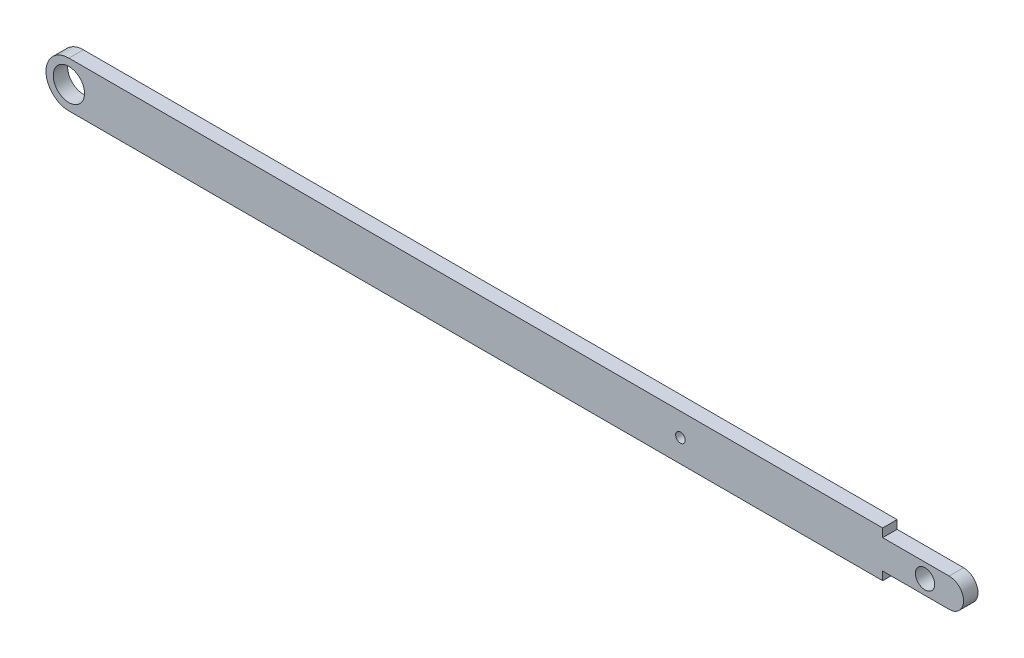
SolidWorks part; units mm, degrees
material "Gray Cast Iron"
ref_plane "Front Plane" through (0, 0, 0) normal (0, 0, 1) x (1, 0, 0)
ref_plane "Top Plane" through (0, 0, 0) normal (0, 1, 0) x (1, 0, 0)
ref_plane "Right Plane" through (0, 0, 0) normal (1, 0, 0) x (0, 0, -1)
sketch "Sketch1" plane through (0, 0, 0) normal (0, 0, 1) x (1, 0, 0)
  line L0 (0, -4.75) -> (169, -4.75)
  line L1 (169, -4.75) -> (169, -3)
  line L2 (169, -3) -> (182.8, -3)
  line L3 (182.8, 3) -> (169, 3)
  line L4 (169, 3) -> (169, 4.75)
  line L5 (169, 4.75) -> (0, 4.75)
  arc A0 (0, 4.75) -> (0, -4.75) centre (0, 0) ccw
  arc A1 (182.8, -3) -> (182.8, 3) centre (182.8, 0) ccw
  dimension "D1" = 4.75
  dimension "D3" = 3
  dimension "D2" = 182.8
  dimension "D4" = 169
extrude "Boss-Extrude1" add sketch "Sketch1" along normal mid plane 3
sketch "Sketch2" plane through (0, 0, 0) normal (0, 0, 1) x (1, 0, 0)
  circle A0 centre (0, 0) radius 3.25
  circle A1 centre (127, 0) radius 1
  circle A2 centre (177.8, 0) radius 2
  dimension "D1" = 6.5
  dimension "D3" = 2
  dimension "D5" = 4
  dimension "D2" = 127
  dimension "D4" = 177.8
extrude "Cut-Extrude1" cut sketch "Sketch2" against normal mid plane 40
